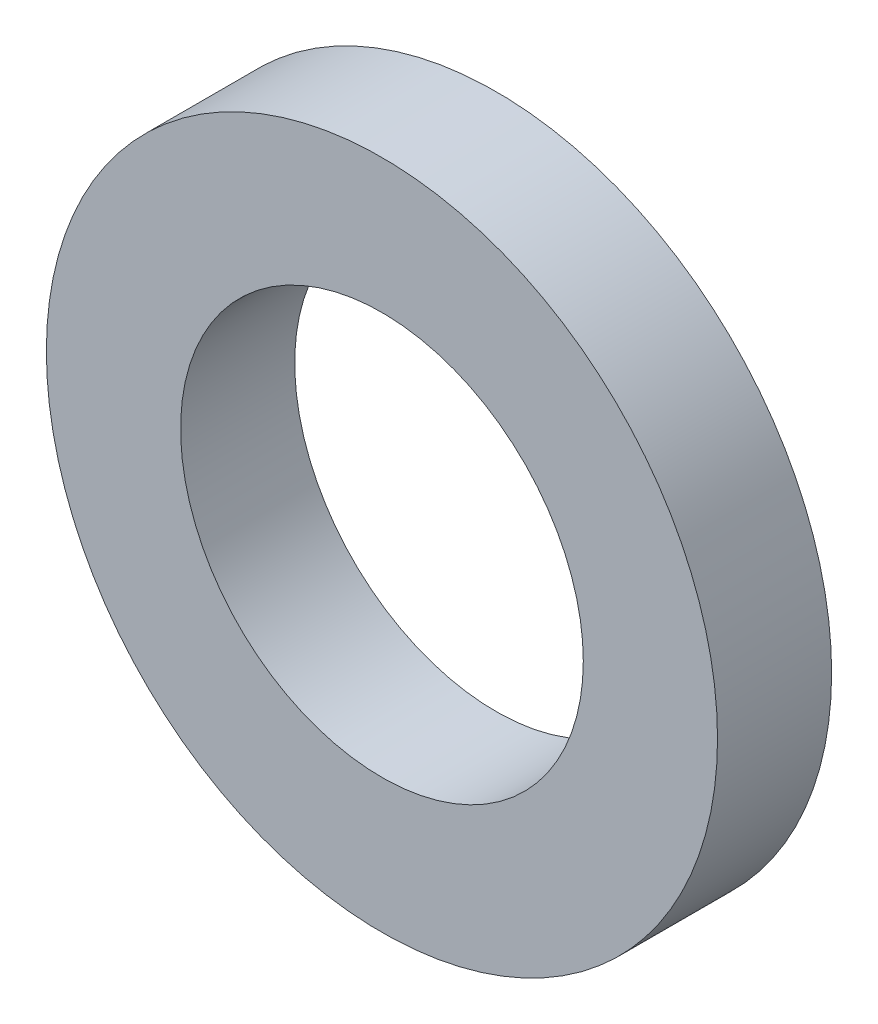
SolidWorks part; units mm, degrees
ref_plane "Front Plane" through (0, 0, 0) normal (0, 0, 1) x (1, 0, 0)
ref_plane "Top Plane" through (0, 0, 0) normal (0, 1, 0) x (1, 0, 0)
ref_plane "Right Plane" through (0, 0, 0) normal (1, 0, 0) x (0, 0, -1)
sketch "Sketch1" plane through (0, 0, 0) normal (0, 0, 1) x (1, 0, 0)
  circle A0 centre (0, 0) radius 3
  circle A1 centre (0, 0) radius 5
  dimension "D1" = 6
  dimension "D2" = 10
extrude "Boss-Extrude1" add sketch "Sketch1" along normal blind 1.7
equation "\"smallPulleyTeeth\"= 15"
equation "\"largePulleyTeeth\"= 30"
equation "\"eighthThick\"= 2.9mm"
equation "\"sixteenthThick\" = 1.7mm"
equation "\"quarterThick\"=5.6mm"
equation "\"OD\" = 150mm"
equation "\"puckAngle\" = 60.5deg"
equation "\"puckDiam\" = 76.5mm"
equation "\"axlePress\" = 5.8mm"
equation "\"press\" = 0.3mm"
equation "\"wheelClear\" = 0.3mm"
equation "\"10-32clear\" = 4.5mm"
equation "\"6-32clear\" = 3.3mm"
equation "\"8-32clear\" = 4.0mm"
equation "\"D1@Boss-Extrude1\"=\"sixteenthThick\""
